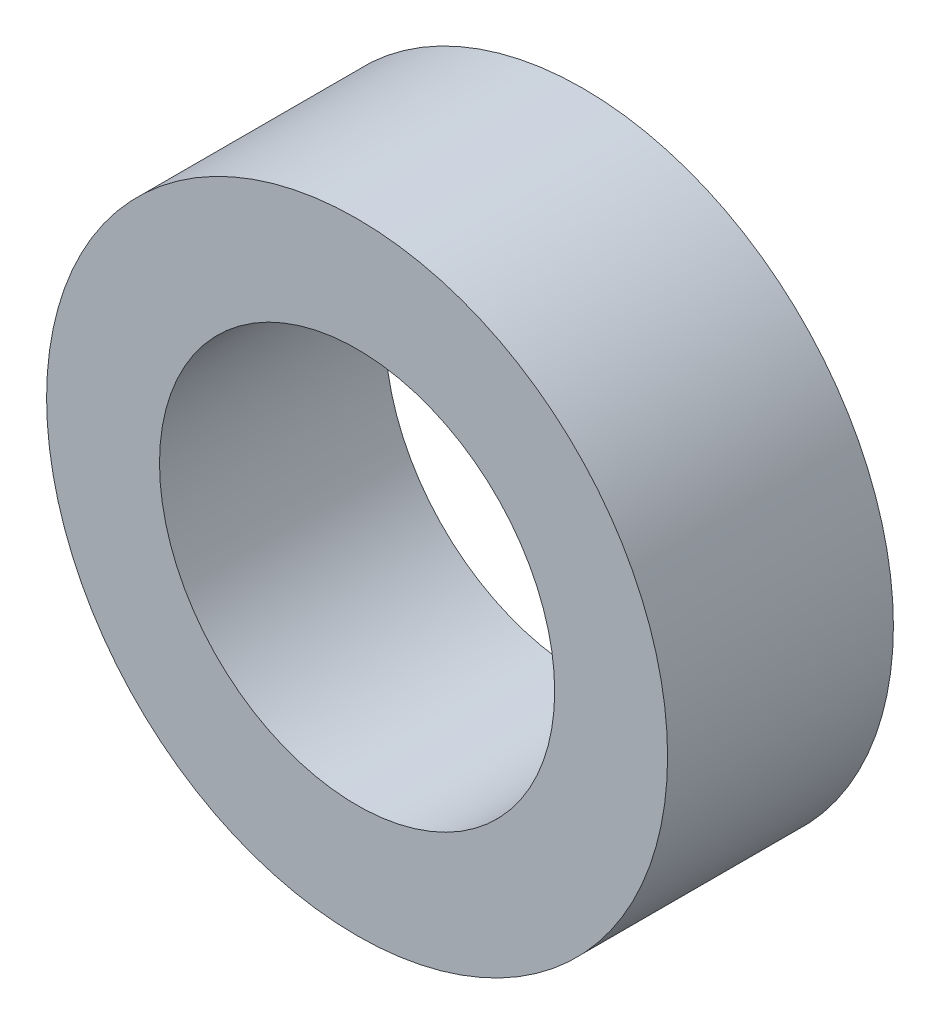
SolidWorks part; units mm, degrees
material "PTFE (general)"
ref_plane "Front Plane" through (0, 0, 0) normal (0, 0, 1) x (1, 0, 0)
ref_plane "Top Plane" through (0, 0, 0) normal (0, 1, 0) x (1, 0, 0)
ref_plane "Right Plane" through (0, 0, 0) normal (1, 0, 0) x (0, 0, -1)
sketch "Sketch1" plane through (0, 0, 0) normal (0, 0, 1) x (1, 0, 0)
  line L0 (-17.4625, 0) -> (17.4625, 0) construction
  line L1 (-11.1125, 0) -> (11.1125, 0) construction
  point P4 (0, 0)
  point P7 (0, 0)
  dimension "OD" = 34.925
  dimension "ID" = 22.225
  dimension "Wall Thickness" = 6.35
sketch "Sketch2" plane through (0, 0, 0) normal (1, 0, 0) x (0, 0, -1)
  line L0 (6.35, 0) -> (-6.35, 0) construction
  point P0 (46.0375, 0)
  point P4 (0, 0)
  point P6 (-46.0375, 0)
  dimension "D1" = 12.7
  dimension "D2" = 52.3875
  dimension "D3" = 52.3875
sketch "Sketch3" plane through (0, 0, 0) normal (0, 0, 1) x (1, 0, 0)
  circle A0 centre (0, 0) radius 17.4625
  circle A1 centre (0, 0) radius 11.1125
  dimension "D1" = 34.925
extrude "Boss-Extrude1" add sketch "Sketch3" along normal mid plane 12.7
equation "\"D2@Sketch2\"=\"OD@Sketch1\" * 1.5"
equation "\"D3@Sketch2\"=\"D2@Sketch2\""
equation "\"D1@Sketch3\" = \"OD@Sketch1\""
equation "\"D1@Boss-Extrude1\"=\"D1@Sketch2\""
